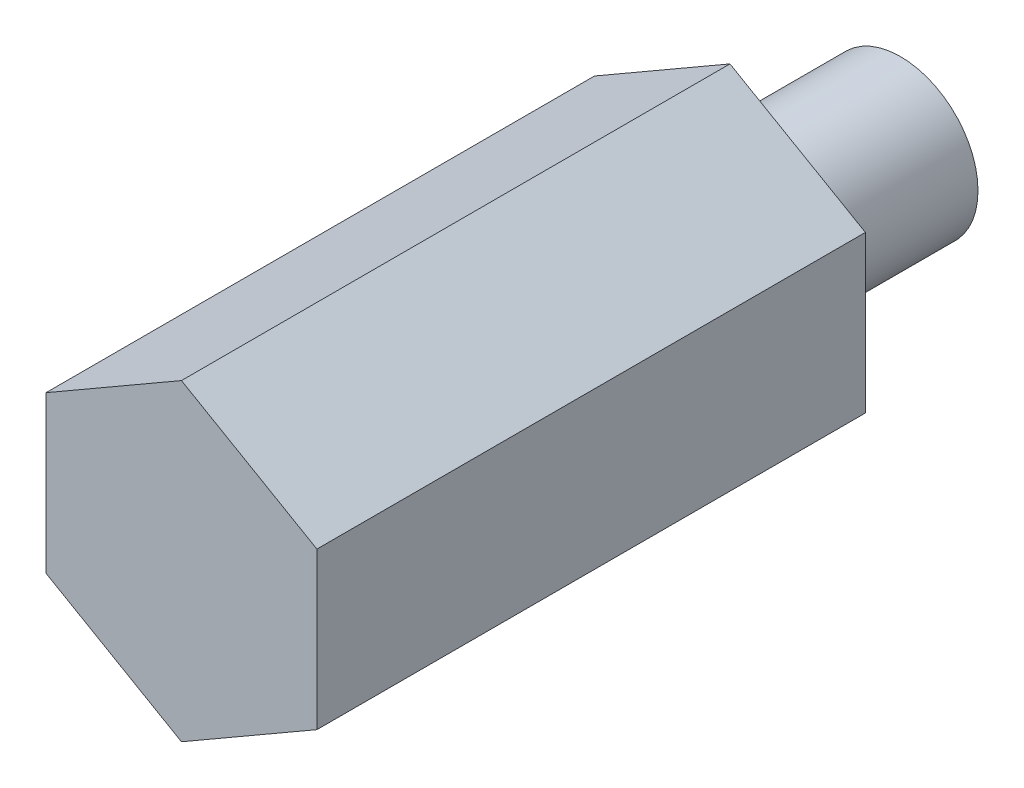
SolidWorks part; units mm, degrees
ref_plane "Front Plane" through (0, 0, 0) normal (0, 0, 1) x (1, 0, 0)
ref_plane "Top Plane" through (0, 0, 0) normal (0, 1, 0) x (1, 0, 0)
ref_plane "Right Plane" through (0, 0, 0) normal (1, 0, 0) x (0, 0, -1)
sketch "Sketch1" plane through (0, 0, 0) normal (0, 0, 1) x (1, 0, 0)
  line L1 (0, 6.4158) -> (-5.5562, 3.2079) construction
  line L2 (-5.5562, 3.2079) -> (-5.5562, -3.2079) construction
  line L3 (-5.5562, -3.2079) -> (0, -6.4158) construction
  line L4 (0, -6.4158) -> (5.5562, -3.2079) construction
  line L5 (5.5562, -3.2079) -> (5.5562, 3.2079) construction
  line L6 (5.5562, 3.2079) -> (0, 6.4158) construction
  circle A2 centre (0, 0) radius 5.5562 construction
  dimension "Width" = 11.1125
sketch "Sketch2" plane through (0, 0, 0) normal (1, 0, 0) x (0, 0, -1)
  line L0 (-11.25, 6.4158) -> (11.25, 6.4158) construction
  point P2 (0, 6.4158)
  point P3 (-16.5312, 6.4158)
  point P4 (16.5312, 6.4158)
  dimension "D2" = 27.7812
  dimension "D1" = 27.7812
sketch "Sketch3" plane through (0, 0, 0) normal (0, 0, 1) x (1, 0, 0)
  line L0 (-5.5562, -3.2079) -> (0, -6.4158) construction
  line L1 (0, -6.4158) -> (5.5562, -3.2079) construction
  line L2 (5.5562, -3.2079) -> (5.5562, 3.2079) construction
  line L3 (5.5562, 3.2079) -> (0, 6.4158) construction
  line L4 (0, 6.4158) -> (-5.5562, 3.2079) construction
  line L5 (-5.5562, 3.2079) -> (-5.5562, -3.2079) construction
  line L6 (-5.5562, -3.2079) -> (0, -6.4158)
  line L7 (0, -6.4158) -> (5.5562, -3.2079)
  line L8 (5.5562, -3.2079) -> (5.5562, 3.2079)
  line L9 (5.5562, 3.2079) -> (0, 6.4158)
  line L10 (0, 6.4158) -> (-5.5562, 3.2079)
  line L11 (-5.5562, 3.2079) -> (-5.5562, -3.2079)
extrude "Boss-Extrude2" add sketch "Sketch3" along normal up to vertex (11.25 mm away) and the other way up to vertex (11.25 mm away) up to point (0, 6.4158, 11.25) other way up to point (0, 6.4158, -11.25)
sketch "Sketch4" plane through (0, 0, -11.25) normal (0, 0, 1) x (1, 0, 0)
  circle A0 centre (0, 0) radius 3.175
  dimension "D1" = 6.35
extrude "Boss-Extrude3" add sketch "Sketch4" against normal blind 7
equation "\"D2@Sketch2\" = \"D1@Sketch2\""
equation "\"D1@Sketch2\" = \"Width@Sketch1\" * 2.5"
